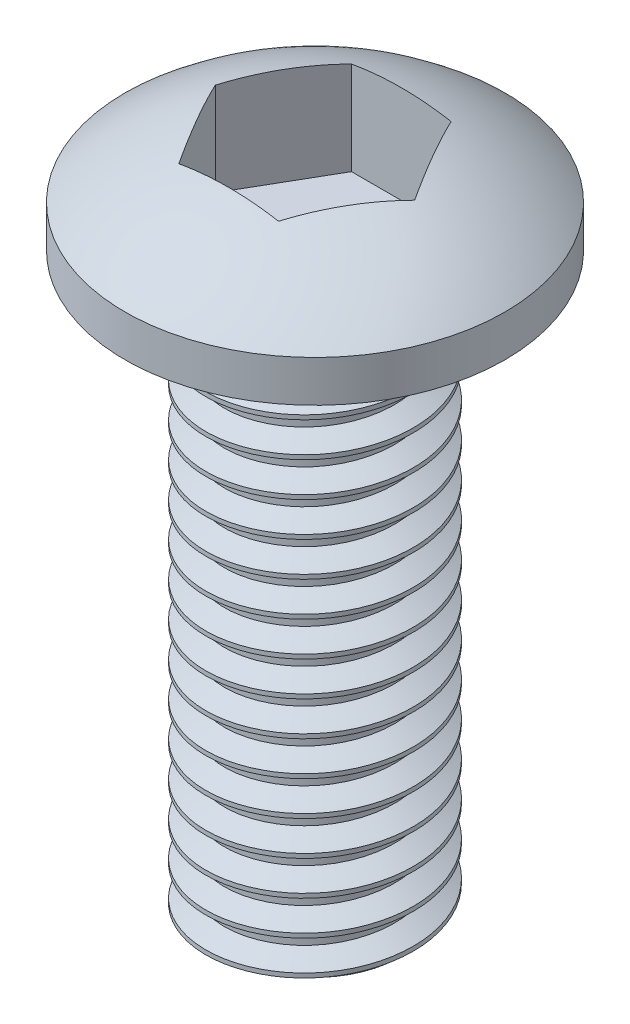
SolidWorks part; units mm, degrees
ref_plane "Plano frontal" through (0, 0, 0) normal (0, 0, 1) x (1, 0, 0)
ref_plane "Plano superior" through (0, 0, 0) normal (0, 1, 0) x (1, 0, 0)
ref_plane "Plano direito" through (0, 0, 0) normal (1, 0, 0) x (0, 0, -1)
sketch "Esboço1" plane through (0, 0, 0) normal (0, 0, 1) x (1, 0, 0)
  line L0 (0, 79.0825) -> (0, -64.0422) construction
sketch "Esboço2" plane through (0, 0, 0) normal (0, 0, 1) x (1, 0, 0)
  line L1 (0, 200079.0825) -> (0, -200064.0422) construction
  line L2 (2.75, 0.6) -> (2.75, 0)
  line L3 (2.75, 0) -> (1.625, 0)
  line L5 (1.5, -8.25) -> (0, -8.25)
  line L6 (0, -8.25) -> (0, 1.6)
  line L7 (0, 0) -> (1.625, 0) construction
  line L8 (1.5, -8.25) -> (1.5, -0.25)
  line L9 (1.5, -0.25) -> (1.625, -0.25)
  line L10 (1.625, -0.25) -> (1.625, 0)
  arc A0 (0, 1.6) -> (2.75, 0.6) centre (0, -2.6813) cw
  dimension "D1" = 0.6
  dimension "D2" = 1.5
  dimension "D3" = 1.6
  dimension "D4" = 8
  dimension "D5" = 0.25
  dimension "D6" = 0.125
  dimension "D7" = 2.75
revolve "Revolução1" add sketch "Esboço2" angle 360 about L0
sketch "Esboço3" plane through (0, 0, 0) normal (0, 1, 0) x (1, 0, 0)
  line L0 (0, 0) -> (-1.4434, 0) construction
  line L1 (-1.4434, 0) -> (-0.7217, -1.25)
  line L2 (-0.7217, -1.25) -> (0.7217, -1.25)
  line L3 (0.7217, -1.25) -> (1.4434, 0)
  line L4 (1.4434, 0) -> (0.7217, 1.25)
  line L5 (0.7217, 1.25) -> (-0.7217, 1.25)
  line L6 (-0.7217, 1.25) -> (-1.4434, 0)
  circle A0 centre (0, 0) radius 1.25 construction
  dimension "D1" = 2.5
extrude "Corte-extrusão1" cut sketch "Esboço3" along normal up to next
thread "Rosca1" pitch 0.5 method cut profile "Perfil da rosca1" start angle 0, offset 0, length 0, pitch 0.5, diameter 3
ref_plane "Plano1" through (-1.5, -0.25, 0) normal (0, 0, 1) x (-1, 0, 0)
sketch "Perfil da rosca1" plane through (-1.5, -0.25, 0) normal (0, 0, 1) x (-1, 0, 0)
  line L0 (0, 0) -> (0, 0.5) construction
  line L11 (0, 0) -> (0, 0.4375)
  line L12 (0, 0.4375) -> (-0.2706, 0.2812)
  line L13 (-0.2706, 0.2812) -> (-0.2706, 0.1562)
  line L15 (-0.2706, 0.1562) -> (0, 0)
  line L17 (-0.2706, 0.2187) -> (0, 0.2187) construction
  point P2 (0, 0)
  dimension "Pitch" = 0.5
  dimension "Profile_Angle" = 60
  dimension "Profile_Land" = 0.125
  dimension "Profile_Height" = 0.2706
